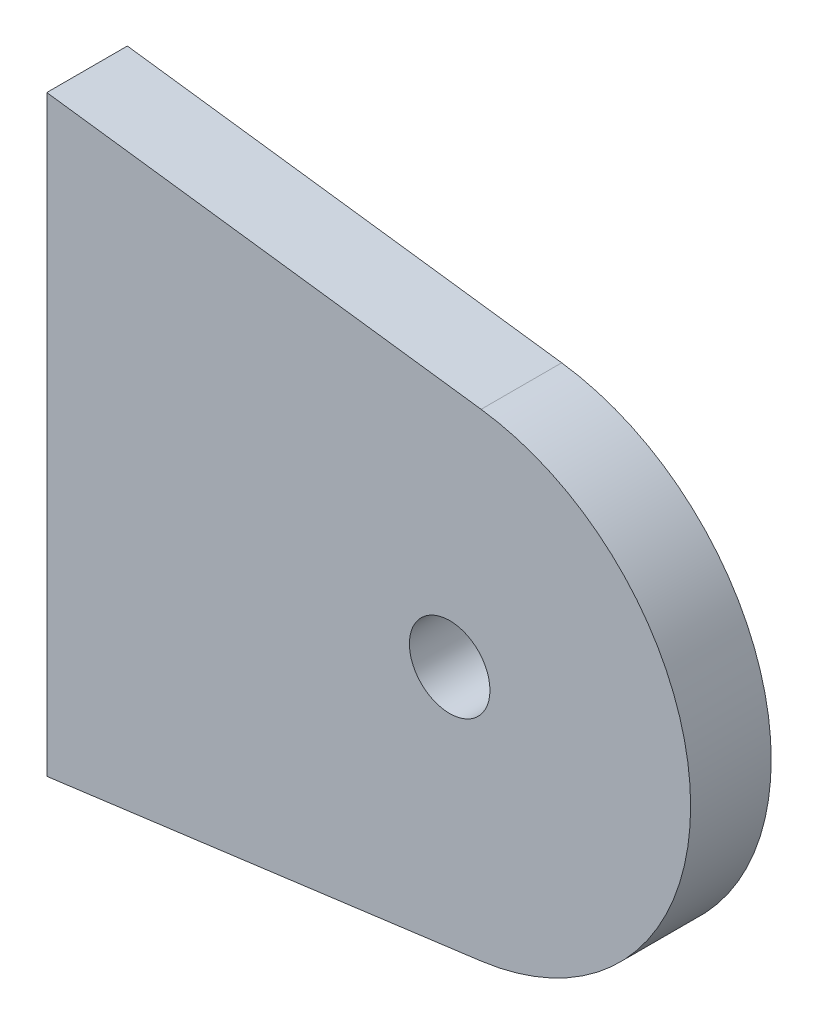
SolidWorks part; units mm, degrees
material "AISI 4130 Steel, annealed at 865C"
ref_plane "X-Y Datum" through (0, 0, 0) normal (0, 0, 1) x (1, 0, 0)
ref_plane "X-Z Datum" through (0, 0, 0) normal (0, 1, 0) x (1, 0, 0)
ref_plane "Y-Z Datum" through (0, 0, 0) normal (1, 0, 0) x (0, 0, -1)
sketch "Sketch1" plane through (-1053.7408, 0, 0) normal (0, 0, 1) x (1, 0, 0)
  line L0 (1054.9803, -9.4147) -> (1037.8658, -11.6679)
  line L1 (1054.9803, 9.4147) -> (1037.8658, 11.6679)
  line L2 (1037.8658, -11.6679) -> (1037.8658, 11.6679)
  circle A0 centre (1053.7408, 0) radius 1.5875
  circle A1 centre (1053.7408, 0) radius 9.4959
  circle A4 centre (1053.7408, 0) radius 11.43 construction
  dimension "D3" = 18.9919
  dimension "D4" = 3.175
  dimension "D5" = 22.86
  dimension "D1" = 15
  dimension "D2" = 15.875
extrude "Boss-Extrude1" add sketch "Sketch1" along normal blind 3.175 contours A1 L1 L2 L0 | A1 | A1 | A1 L1 | A0 region at (-11.2112, 0, 0) region at (-9.2273, 0, 0)
